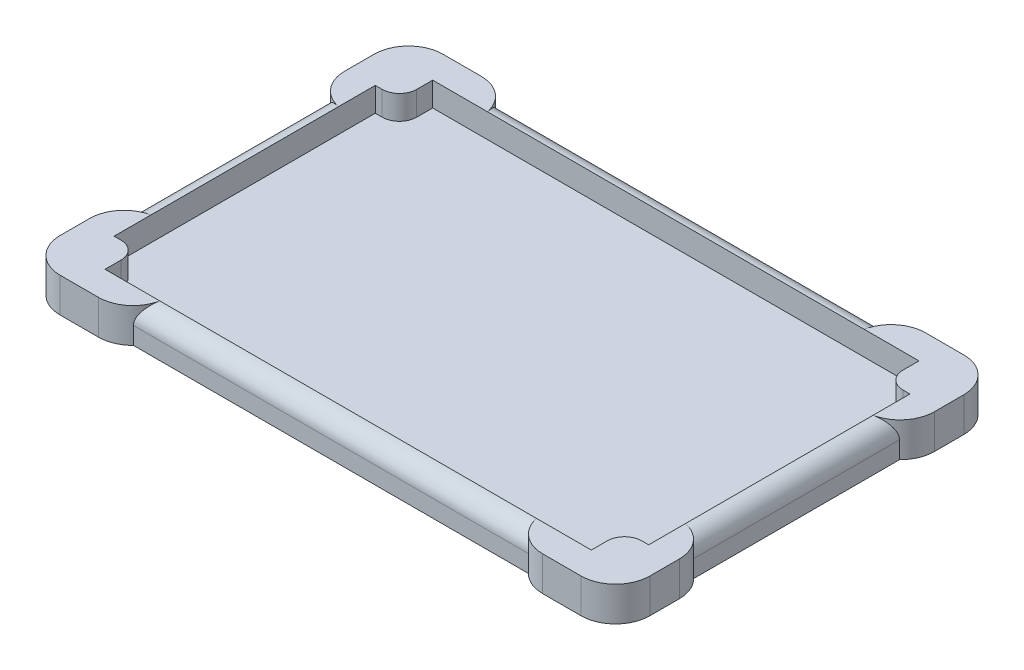
SolidWorks part; units mm, degrees
ref_plane "Front Plane" through (0, 0, 0) normal (0, 0, 1) x (1, 0, 0)
ref_plane "Top Plane" through (0, 0, 0) normal (0, 1, 0) x (1, 0, 0)
ref_plane "Right Plane" through (0, 0, 0) normal (1, 0, 0) x (0, 0, -1)
sketch "Sketch7" plane through (0, 0, 0) normal (0, 1, 0) x (1, 0, 0)
  line L0 (0, 0) -> (0, 85)
  line L1 (0, 85) -> (145, 85)
  line L2 (145, 85) -> (145, 0)
  line L3 (145, 0) -> (0, 0)
  line L4 (-10, 95) -> (155, 95)
  line L5 (155, 95) -> (155, -10)
  line L6 (155, -10) -> (-10, -10)
  line L7 (-10, -10) -> (-10, 95)
  dimension "D1" = 85
  dimension "D2" = 145
  dimension "D3" = 10
extrude "Boss-Extrude7" add sketch "Sketch7" along normal blind 10 contours L3 L2 L1 L0 | L7 L6 L5 L4 L2 L3 L0 L1 region at (72.5, 0, -42.5) region at (72.5, 0, -93.0442)
sketch "Sketch8" plane through (0, 10, 0) normal (0, 1, 0) x (1, 0, 0)
  line L0 (155, -10) -> (-10, -10) construction
  line L1 (-13, -13) -> (15.2279, -13)
  line L2 (-13, -13) -> (-13, 12.6402)
  line L3 (-13, 12.6402) -> (15.2279, 12.6402)
  line L4 (15.2279, -13) -> (15.2279, 12.6402)
  line L5 (-10, -10) -> (-10, 95) construction
  line L6 (72.5, -10) -> (72.5, 95) construction
  line L7 (-10, 95) -> (155, 95) construction
  line L8 (-10, 42.5) -> (155, 42.5) construction
  line L9 (155, 95) -> (155, -10) construction
  line L10 (129.7721, -13) -> (129.7721, 12.6402)
  line L11 (158, -13) -> (129.7721, -13)
  line L12 (158, -13) -> (158, 12.6402)
  line L13 (158, 12.6402) -> (129.7721, 12.6402)
  line L14 (158, 98) -> (129.7721, 98)
  line L15 (158, 98) -> (158, 72.3598)
  line L16 (158, 72.3598) -> (129.7721, 72.3598)
  line L17 (129.7721, 98) -> (129.7721, 72.3598)
  line L18 (-13, 98) -> (-13, 72.3598)
  line L19 (-13, 98) -> (15.2279, 98)
  line L20 (15.2279, 98) -> (15.2279, 72.3598)
  line L21 (-13, 72.3598) -> (15.2279, 72.3598)
  dimension "D1" = 3
  dimension "D2" = 3
extrude "Boss-Extrude8" add sketch "Sketch8" against normal blind 10
sketch "Sketch10" plane through (0, 10, 0) normal (0, 1, 0) x (1, 0, 0)
  line L0 (15.2279, 95) -> (129.7721, 95) construction
  line L1 (2, -5) -> (143, -5)
  line L2 (2, -5) -> (2, 4.63)
  line L3 (2, 90) -> (143, 90)
  line L4 (143, -5) -> (143, 4.63)
  line L7 (129.7721, -10) -> (15.2279, -10) construction
  line L8 (-13, 12.6402) -> (-13, -13) construction
  line L10 (158, -13) -> (158, 12.6402) construction
  line L13 (-10, 12.6402) -> (-10, 72.3598) construction
  line L14 (2, 4.63) -> (-5, 4.63)
  line L16 (2, 80.37) -> (-5, 80.37)
  line L17 (-5, 4.63) -> (-5, 80.37)
  line L18 (3.3463, 35.2165) -> (2, 42.5) construction
  line L20 (2, 80.37) -> (2, 90)
  line L21 (143, 4.63) -> (150, 4.63)
  line L22 (150, 4.63) -> (150, 80.37)
  line L23 (143, 80.37) -> (150, 80.37)
  line L24 (143, 80.37) -> (143, 90)
  point P0 (72.5, 42.5)
  point P13 (2, 42.5)
  dimension "D1" = 5
  dimension "D2" = 5
  dimension "D3" = 15
  dimension "D4" = 15
  dimension "D5" = 5
extrude "Cut-Extrude4" cut sketch "Sketch10" against normal blind 7
fillet "Fillet2" radius 10 12 edges at (-13, 5, -72.3598) (15.2279, 5, -98) (-13, 5, -98) (158, 5, -98) (129.7721, 5, -98) (-13, 5, 13) (-13, 5, -12.6402) (158, 5, -72.3598) (158, 5, -12.6402) (158, 5, 13) (129.7721, 5, 13) (15.2279, 5, 13)
fillet "Fillet3" radius 5 4 edges at (2, 6.5, -4.63) (2, 6.5, -80.37) (143, 6.5, -80.37) (143, 6.5, -4.63)
fillet "Fillet6" radius 5 4 edges at (155, 10, -42.5) (72.5, 10, 10) (72.5, 10, -95) (-10, 10, -42.5)
